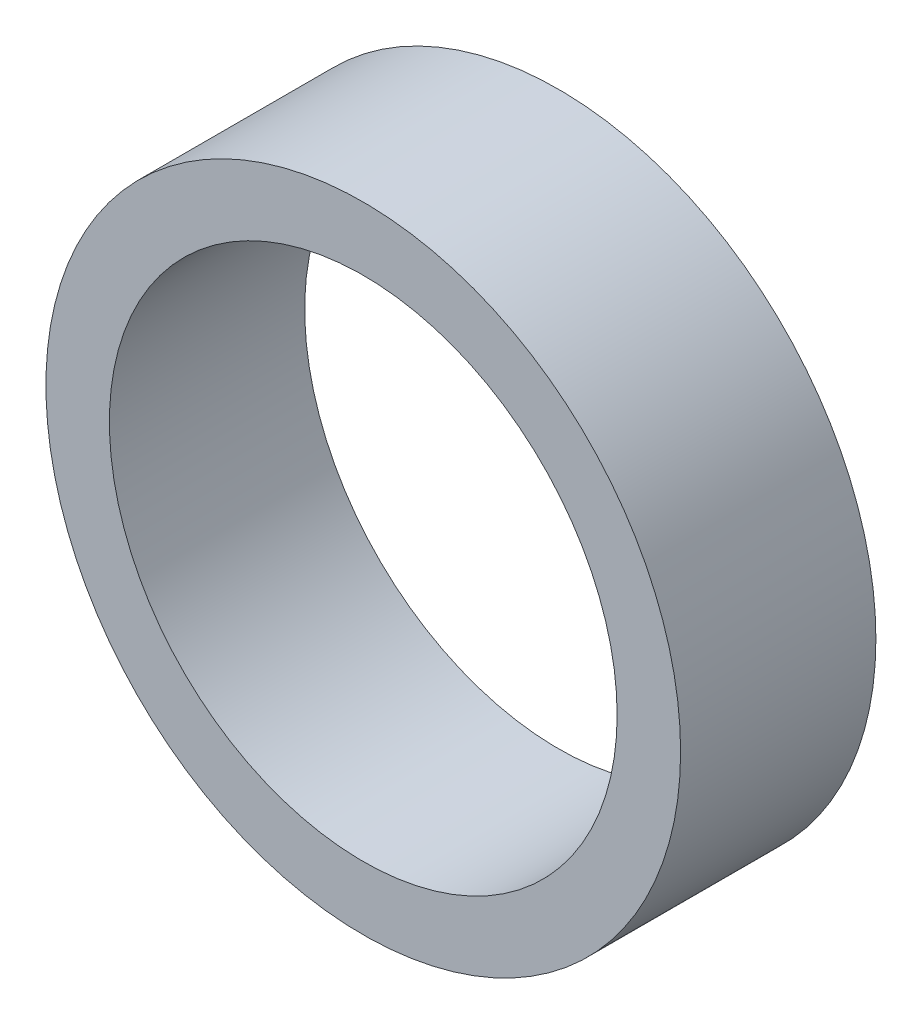
SolidWorks part; units mm, degrees
ref_plane "Front Plane" through (0, 0, 0) normal (0, 0, 1) x (1, 0, 0)
ref_plane "Top Plane" through (0, 0, 0) normal (0, 1, 0) x (1, 0, 0)
ref_plane "Right Plane" through (0, 0, 0) normal (1, 0, 0) x (0, 0, -1)
sketch "Sketch1" plane through (0, 0, 3) normal (0, 0, 1) x (1, 0, 0)
  circle A0 centre (33, 0) radius 3.25
  circle A1 centre (33, 0) radius 2.6
  dimension "D1" = 6.5
  dimension "D2" = 5.2
extrude "Boss-Extrude1" add sketch "Sketch1" along normal blind 2 from offset 5
